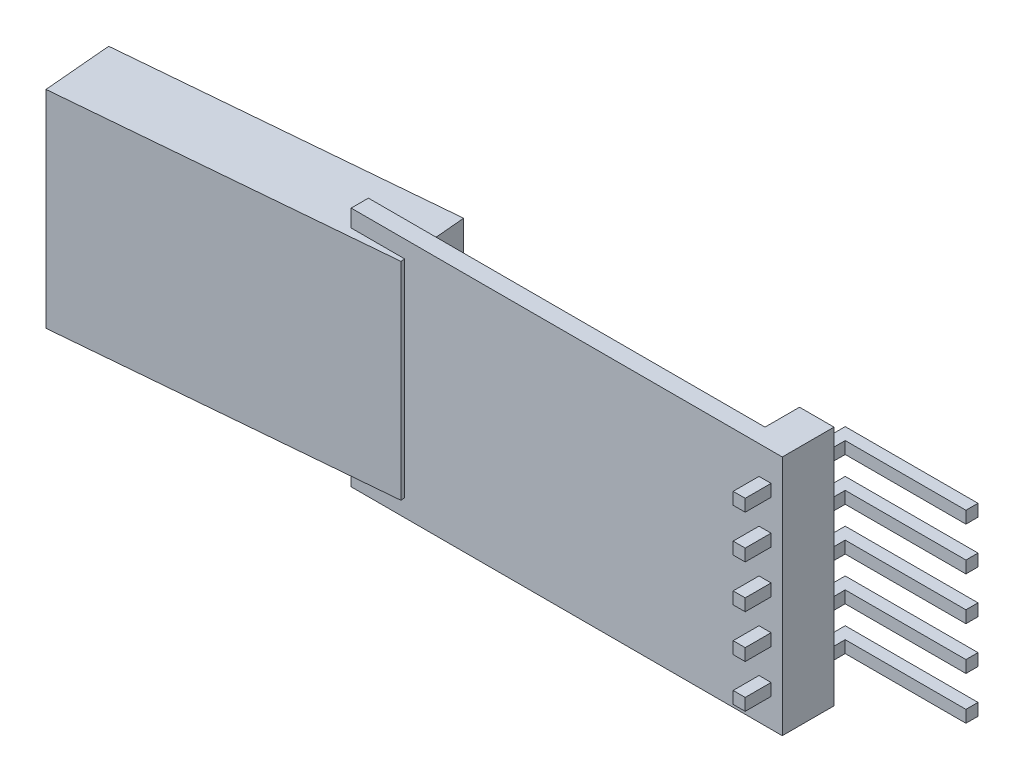
SolidWorks part; units mm, degrees
ref_plane "Спереди" through (0, 0, 0) normal (0, 0, 1) x (1, 0, 0)
ref_plane "Сверху" through (0, 0, 0) normal (0, 1, 0) x (1, 0, 0)
ref_plane "Справа" through (0, 0, 0) normal (1, 0, 0) x (0, 0, -1)
sketch "Эскиз1" plane through (0, 0, 0) normal (0, 0, 1) x (1, 0, 0)
  line L0 (-1, 14.01) -> (-1, -0.01) construction
  line L1 (0, 0) -> (-25, 0)
  line L2 (0, 0) -> (0, 14)
  line L3 (0, 14) -> (-25, 14)
  line L4 (-25, 0) -> (-25, 14)
  line L5 (0, 14) -> (-2, 14)
  line L6 (0, 14) -> (0, 0)
  line L7 (0, 0) -> (-2, 0)
  line L8 (-2, 14) -> (-2, 0)
  line L9 (-1.35, 4.15) -> (-1.35, 4.85)
  line L10 (-1.35, 1.65) -> (-0.65, 1.65)
  line L11 (-1.35, 1.65) -> (-1.35, 2.35)
  line L12 (-1.35, 2.35) -> (-0.65, 2.35)
  line L13 (-0.65, 1.65) -> (-0.65, 2.35)
  line L14 (-1.35, 1.65) -> (-0.65, 2.35) construction
  line L15 (-1.35, 2.35) -> (-0.65, 1.65) construction
  line L16 (-1.35, 4.15) -> (-0.65, 4.15)
  line L17 (-0.65, 4.15) -> (-0.65, 4.85)
  line L18 (-1.35, 4.85) -> (-0.65, 4.85)
  line L19 (-1.35, 4.85) -> (-0.65, 4.15) construction
  line L20 (-1.35, 4.15) -> (-0.65, 4.85) construction
  line L21 (-1.35, 6.65) -> (-1.35, 7.35)
  line L22 (-1.35, 6.65) -> (-0.65, 6.65)
  line L23 (-0.65, 6.65) -> (-0.65, 7.35)
  line L24 (-1.35, 7.35) -> (-0.65, 7.35)
  line L25 (-1.35, 7.35) -> (-0.65, 6.65) construction
  line L26 (-1.35, 6.65) -> (-0.65, 7.35) construction
  line L27 (-1.35, 9.15) -> (-1.35, 9.85)
  line L28 (-1.35, 9.15) -> (-0.65, 9.15)
  line L29 (-0.65, 9.15) -> (-0.65, 9.85)
  line L30 (-1.35, 9.85) -> (-0.65, 9.85)
  line L31 (-1.35, 9.85) -> (-0.65, 9.15) construction
  line L32 (-1.35, 9.15) -> (-0.65, 9.85) construction
  line L33 (-1.35, 11.65) -> (-1.35, 12.35)
  line L34 (-1.35, 11.65) -> (-0.65, 11.65)
  line L35 (-0.65, 11.65) -> (-0.65, 12.35)
  line L36 (-1.35, 12.35) -> (-0.65, 12.35)
  line L37 (-1.35, 12.35) -> (-0.65, 11.65) construction
  line L38 (-1.35, 11.65) -> (-0.65, 12.35) construction
  line L39 (-26.2625, 7) -> (1.3556, 7) construction
  point P11 (-1, 2)
  point P32 (-25, 7)
  point P33 (-1, 7)
  point P34 (-0.65, 4.5)
  point P35 (-16.7793, 8.6901)
  point P36 (-12.2648, 7.26)
  point P37 (-0.65, 2)
  point P38 (-0.65, 7)
  dimension "D1" = 25
  dimension "D2" = 14
  dimension "D3" = 2
  dimension "D4" = 0.7
  dimension "D6" = 2.5
  dimension "D5" = 5
extrude "Бобышка-Вытянуть1" add sketch "Эскиз1" along normal blind 1 contours L8 L3 L4 L1 | L3 L8 L1 L2 L13 L10 L11 L12 L9 L18 L17 L16 L21 L24 L23 L22 L27 L30 L29 L28 L33 L36 L35 L34 | L36 L33 L34 L35 | L30 L27 L28 L29 | L24 L21 L22 L23 | L18 L9 L16 L17 | L10 L13 L12 L11 region at (-1, 0.1414, 0) region at (-13.5, 7, 0) region at (-1, 4.5, 0) region at (-1, 2, 0) region at (-1, 7, 0) region at (-1, 9.5, 0) region at (-1, 12, 0)
extrude "Бобышка-Вытянуть2" add sketch "Эскиз1<3>" against normal blind 2 contours L3 L8 L1 L2 L13 L10 L11 L12 L9 L18 L17 L16 L21 L24 L23 L22 L27 L30 L29 L28 L33 L36 L35 L34 region at (-1, 0.1414, 0)
sketch "Эскиз1<3>" plane through (0, 0, 0) normal (0, 0, 1) x (1, 0, 0) same geometry as "Эскиз1"
extrude "Бобышка-Вытянуть3" add sketch "Эскиз1<4>" along normal blind 2.5 contours L36 L33 L34 L35 | L30 L27 L28 L29 | L24 L21 L22 L23 | L18 L9 L16 L17 | L10 L13 L12 L11 region at (-1, 4.5, 0) region at (-1, 2, 0) region at (-1, 7, 0) region at (-1, 9.5, 0) region at (-1, 12, 0)
sketch "Эскиз1<4>" plane through (0, 0, 0) normal (0, 0, 1) x (1, 0, 0) same geometry as "Эскиз1"
extrude "Бобышка-Вытянуть4" add sketch "Эскиз1<5>" against normal blind 4 contours L36 L33 L34 L35 | L30 L27 L28 L29 | L24 L21 L22 L23 | L18 L9 L16 L17 | L10 L13 L12 L11 region at (-1, 4.5, 0) region at (-1, 2, 0) region at (-1, 7, 0) region at (-1, 9.5, 0) region at (-1, 12, 0)
sketch "Эскиз1<5>" plane through (0, 0, 0) normal (0, 0, 1) x (1, 0, 0) same geometry as "Эскиз1"
sketch "Эскиз2" plane through (-0.65, 0, 0) normal (1, 0, 0) x (0, 0, -1)
  line L0 (4, 11.65) -> (2, 11.65) construction
  line L1 (4, 12.35) -> (3.3, 12.35)
  line L2 (4, 12.35) -> (4, 11.65)
  line L3 (4, 11.65) -> (3.3, 11.65)
  line L4 (3.3, 12.35) -> (3.3, 11.65)
  line L5 (4, 9.85) -> (3.3, 9.85)
  line L6 (4, 9.85) -> (4, 9.15)
  line L7 (4, 9.15) -> (3.3, 9.15)
  line L8 (3.3, 9.85) -> (3.3, 9.15)
  line L9 (4, 7.35) -> (3.3, 7.35)
  line L10 (4, 7.35) -> (4, 6.65)
  line L11 (4, 6.65) -> (3.3, 6.65)
  line L12 (3.3, 7.35) -> (3.3, 6.65)
  line L13 (4, 4.85) -> (3.3, 4.85)
  line L14 (4, 4.85) -> (4, 4.15)
  line L15 (4, 4.15) -> (3.3, 4.15)
  line L16 (3.3, 4.85) -> (3.3, 4.15)
  line L17 (4, 2.35) -> (3.3, 2.35)
  line L18 (4, 2.35) -> (4, 1.65)
  line L19 (4, 1.65) -> (3.3, 1.65)
  line L20 (3.3, 2.35) -> (3.3, 1.65)
  point P7 (4, 9.5)
  point P8 (4, 12)
  dimension "D2" = 2.5
  dimension "D1" = 5
extrude "Бобышка-Вытянуть5" add sketch "Эскиз2" along normal blind 7
sketch "Эскиз3" plane through (0, 0, 0) normal (0, -1, 0) x (1, 0, 0)
  line L0 (-25, 0) -> (-32.6647, 0.6706) construction
  line L1 (-2, 0) -> (-25, 0) construction
  point P3 (-32.6275, 1.0097)
  dimension "D1" = 5
ref_axis "Ось1" through (-25, 0, 0) along (-0.9962, 0, 0.0872)
ref_plane "Плоскость1" through (-0.1899, 0, -2.1706) normal (-0.0872, 0, -0.9962) x (-0.9962, 0, 0.0872)
sketch "Эскиз4" plane through (-0.1899, 0, -2.1706) normal (-0.0872, 0, -0.9962) x (-0.9962, 0, 0.0872)
  line L0 (24.9049, 0) -> (24.9049, 14) construction
  line L1 (21.9049, 13) -> (40.9049, 13)
  line L2 (21.9049, 13) -> (21.9049, 1)
  line L3 (21.9049, 1) -> (40.9049, 1)
  line L4 (40.9049, 13) -> (40.9049, 1)
  line L5 (42.6088, 7) -> (20.612, 7) construction
  line L6 (1.9924, 14) -> (24.9049, 14) construction
  line L7 (1.9924, 0) -> (24.9049, 0) construction
  point P8 (40.9049, 7)
  dimension "D1" = 12
  dimension "D2" = 19
  dimension "D3" = 16
extrude "Бобышка-Вытянуть6" add sketch "Эскиз4" along normal blind 2.5 separate body
extrude "Бобышка-Вытянуть7" add sketch "Эскиз4<2>" against normal blind 1.5
sketch "Эскиз4<2>" plane through (-0.1899, 0, -2.1706) normal (-0.0872, 0, -0.9962) x (-0.9962, 0, 0.0872) same geometry as "Эскиз4"
